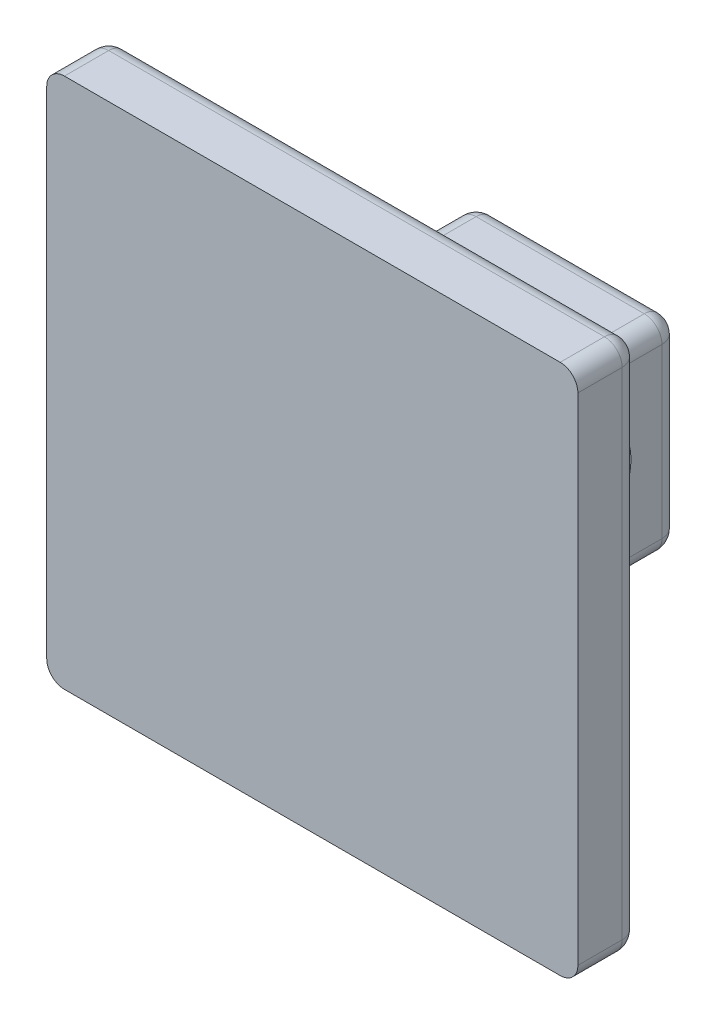
SolidWorks part; units mm, degrees
ref_plane "Plano frontal" through (0, 0, 0) normal (0, 0, 1) x (1, 0, 0)
ref_plane "Plano superior" through (0, 0, 0) normal (0, 1, 0) x (1, 0, 0)
ref_plane "Plano direito" through (0, 0, 0) normal (1, 0, 0) x (0, 0, -1)
sketch "Esboço1" plane through (0, 0, 0) normal (0, 0, 1) x (1, 0, 0)
  line L1 (-11.5, -11.5) -> (11.5, -11.5)
  line L2 (-11.5, -11.5) -> (-11.5, 11.5)
  line L3 (-11.5, 11.5) -> (11.5, 11.5)
  line L4 (11.5, -11.5) -> (11.5, 11.5)
  line L5 (-11.5, -11.5) -> (11.5, 11.5) construction
  line L6 (-11.5, 11.5) -> (11.5, -11.5) construction
  point P0 (0, 0)
  dimension "D1" = 23
  dimension "D2" = 23
extrude "Ressalto-extrusão1" add sketch "Esboço1" along normal blind 23
sketch "Esboço3" plane through (0, 0, 23) normal (0, 0, 1) x (1, 0, 0)
  line L1 (30, -30) -> (-30, -30)
  line L2 (30, -30) -> (30, 30)
  line L3 (30, 30) -> (-30, 30)
  line L4 (-30, -30) -> (-30, 30)
  line L5 (30, -30) -> (-30, 30) construction
  line L6 (30, 30) -> (-30, -30) construction
  point P0 (0, 0)
  dimension "D1" = 60
  dimension "D2" = 60
extrude "Ressalto-extrusão2" add sketch "Esboço3" along normal blind 7
sketch "Esboço6" plane through (11.5, 0, 0) normal (1, 0, 0) x (0, 0, -1)
  line L0 (-23, 11.5) -> (0, -11.5) construction
  line L1 (0, 11.5) -> (-23, -11.5) construction
  line L2 (-23, -11.5) -> (0, -11.5) construction
  line L3 (-23, -11.5) -> (-23, 11.5) construction
  circle A0 centre (-11.5, 0) radius 6
  dimension "D1" = 12
extrude "Corte-extrusão1" cut sketch "Esboço6" against normal up to next (23 mm away)
fillet "Filete1" radius 2 4 edges at (30, 0, 23) (0, -30, 23) (-30, 0, 23) (0, 30, 23)
fillet "Filete2" radius 2 8 edges at (29.4142, -29.4142, 23.5858) (29.4142, 29.4142, 23.5858) (-29.4142, 29.4142, 23.5858) (-29.4142, -29.4142, 23.5858) (30, -30, 27.5) (30, 30, 27.5) (-30, 30, 27.5) (-30, -30, 27.5)
fillet "Filete3" radius 2 8 edges at (-11.5, 0, 0) (0, 11.5, 0) (11.5, 0, 0) (0, -11.5, 0) (11.5, -11.5, 11.5) (-11.5, -11.5, 11.5) (-11.5, 11.5, 11.5) (11.5, 11.5, 11.5)
